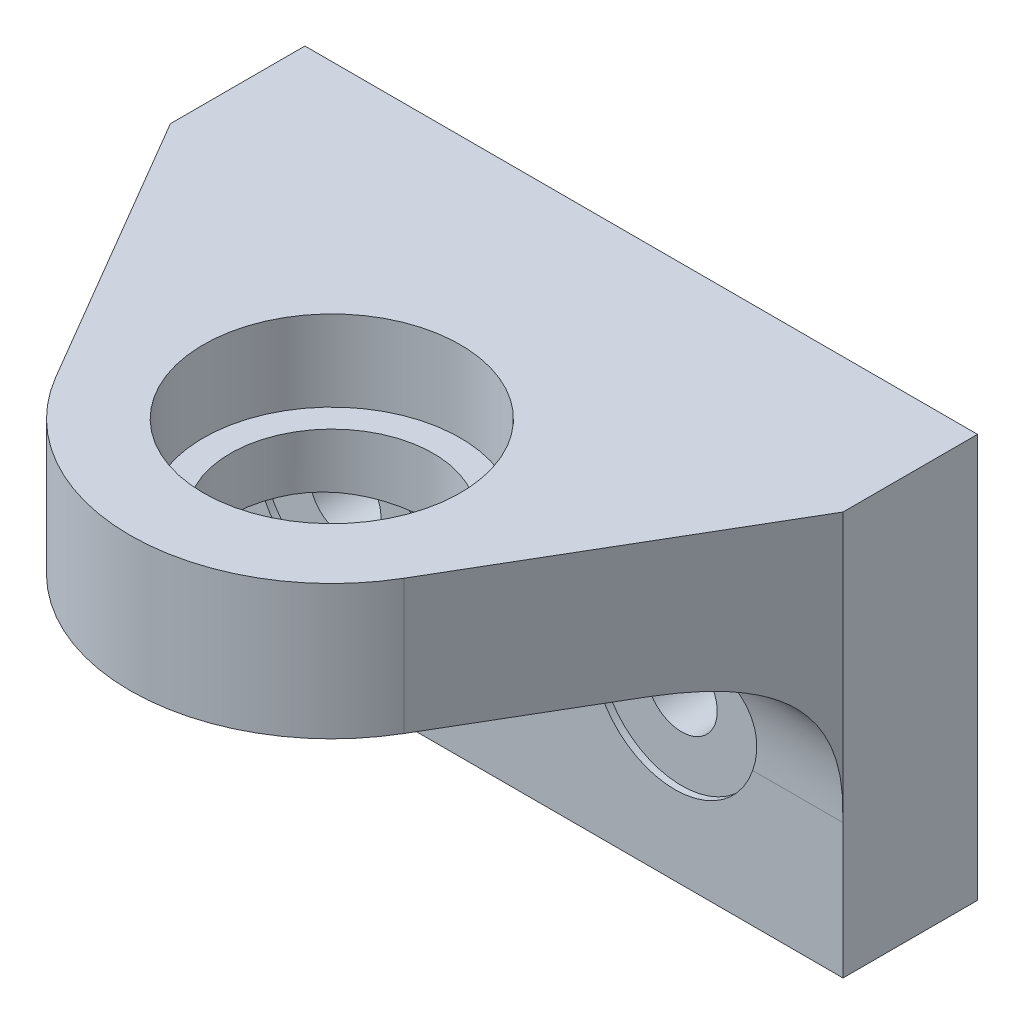
SolidWorks part; units mm, degrees
material "PET"
ref_plane "Front Plane" through (0, 0, 0) normal (0, 0, 1) x (1, 0, 0)
ref_plane "Top Plane" through (0, 0, 0) normal (0, 1, 0) x (1, 0, 0)
ref_plane "Right Plane" through (0, 0, 0) normal (1, 0, 0) x (0, 0, -1)
sketch "Sketch1" plane through (0, 0, 0) normal (0, 0, 1) x (1, 0, 0)
  line L1 (-25, 15) -> (25, 15)
  line L2 (-25, 15) -> (-25, -15)
  line L3 (-25, -15) -> (25, -15)
  line L4 (25, 15) -> (25, -15)
  line L5 (-25, 15) -> (25, -15) construction
  line L6 (-25, -15) -> (25, 15) construction
  point P0 (0, 0)
  dimension "D1" = 50
  dimension "D2" = 30
extrude "Boss-Extrude1" add sketch "Sketch1" along normal blind 10
sketch "Sketch8" plane through (0, 15, 0) normal (0, 1, 0) x (1, 0, 0)
  line L0 (-25, -10) -> (-12.9427, -30.582)
  line L5 (12.9427, -30.582) -> (25, -10)
  line L6 (25, -10) -> (-25, -10)
  line L7 (0, -10) -> (0, -38) construction
  line L8 (25, 0) -> (-25, 0) construction
  arc A0 (-12.9427, -30.582) -> (12.9427, -30.582) centre (0, -23) ccw
  dimension "D2" = 30
  dimension "D1" = 23
extrude "Boss-Extrude3" add sketch "Sketch8" against normal blind 10
sketch "Sketch14" plane through (0, 0, 10) normal (0, 0, 1) x (1, 0, 0)
  line L0 (-25, -3) -> (-12.5, -3) construction
  line L2 (-12.5, -3) -> (12.5, -3) construction
  line L3 (12.5, -3) -> (25, -3) construction
  line L5 (-25, 5) -> (-25, -15) construction
  line L6 (25, -15) -> (25, 5) construction
  point P2 (-12.5, -3)
  point P6 (12.5, -3)
  point P18 (-12.5, -3)
  point P20 (12.5, -3)
  dimension "D1" = 25
  dimension "D2" = 12
hole_wizard "CBORE for M5 Hex Head Bolt1" positions "Sketch14" profile "Sketch10" counterbore size "M5" standard "ANSI Metric" end condition through all
sketch "Sketch10" plane through (12.5, -3, 10) normal (1, 0, 0) x (0, -1, 0)
  line L0 (0, 0) -> (0, 10)
  line L1 (0, 10) -> (2.65, 10)
  line L3 (2.65, 10) -> (2.65, 0.5)
  line L4 (2.65, 0.5) -> (6.12, 0.5)
  line L5 (6.12, 0.5) -> (6.12, 0)
  line L7 (6.12, 0) -> (0, 0)
  line L11 (0, -6.35) -> (0, 107.95) construction
  dimension "Thru Hole Dia." = 5.3
  dimension "Thru Hole Depth" = 10
  dimension "C'Bore Dia." = 12.24
  dimension "C'Bore Depth" = 0.5
fillet "Fillet1" radius 10 1 edges at (0, 5, 10) curvature continuous yes
sketch "Sketch15" plane through (0, 15, 0) normal (0, 1, 0) x (1, 0, 0)
  circle A0 centre (0, -23) radius 9.55
  arc A3 (-12.9427, -30.582) -> (12.9427, -30.582) centre (0, -23) ccw construction
  dimension "D1" = 19.1
extrude "Cut-Extrude1" cut sketch "Sketch15" against normal blind 6
sketch "Sketch16" plane through (0, 9, 0) normal (0, 1, 0) x (1, 0, 0)
  circle A0 centre (0, -23) radius 7.55
  circle A1 centre (0, -23) radius 9.55 construction
  dimension "D1" = 2
extrude "Cut-Extrude2" cut sketch "Sketch16" against normal through all
